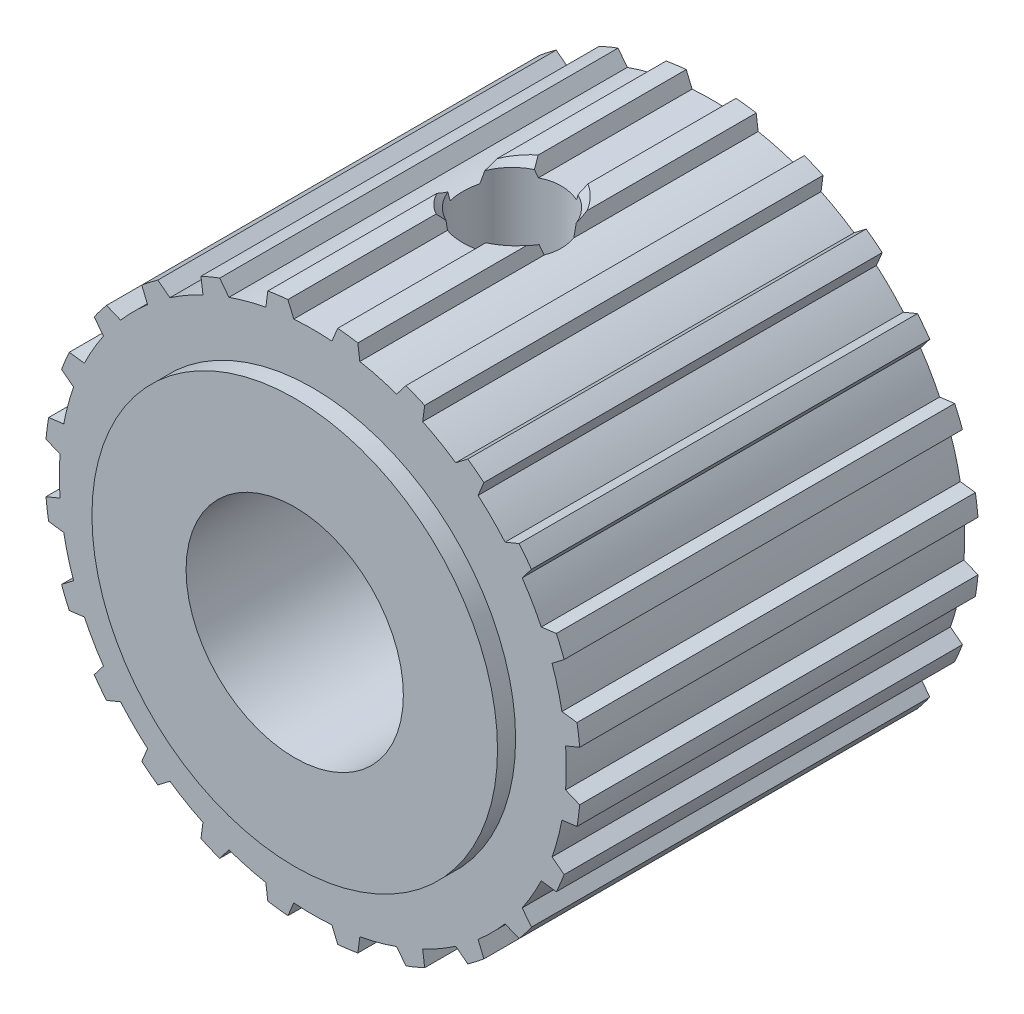
SolidWorks part; units mm, degrees
ref_plane "Face" through (0, 0, 0) normal (0, 0, 1) x (1, 0, 0)
ref_plane "Dessus" through (0, 0, 0) normal (0, 1, 0) x (1, 0, 0)
ref_plane "Droite" through (0, 0, 0) normal (1, 0, 0) x (0, 0, -1)
sketch "Esquisse1" plane through (0, 0, 0) normal (0, 0, 1) x (1, 0, 0)
  line L0 (0, 0) -> (0, 69.2099) construction
  circle A0 centre (0, 0) radius 7.5
  circle A1 centre (0, 0) radius 18.5
  dimension "D1" = 37
  dimension "D2" = 15
extrude "Base-Extrusion" add sketch "Esquisse1" along normal mid plane 30
sketch "Esquisse9" plane through (0, 0, 0) normal (1, 0, 0) x (0, 0, -1)
  line L0 (-15, 18.5) -> (15, 18.5)
  line L1 (-15, 18.5) -> (15, 18.5)
  line L2 (15, -18.5) -> (-15, -18.5)
sketch "Esquisse2" plane through (0, 0, 15) normal (0, 0, 1) x (1, 0, 0)
  line L0 (0, 0) -> (-2.4147, 18.3417) construction
  line L1 (0, 0) -> (2.4147, 18.3417) construction
  line L2 (1.3172, 17.4504) -> (1.7188, 18.42)
  line L3 (-1.3168, 17.4504) -> (-1.7184, 18.42)
  line L4 (0.0002, 17.5) -> (0.0002, 18.5) construction
  arc A0 (1.3172, 17.4504) -> (-1.3168, 17.4504) centre (0, 0) ccw
  circle A1 centre (0, 0) radius 18.5 construction
  arc A3 (1.7188, 18.42) -> (-1.7184, 18.42) centre (0, 0) ccw
  dimension "D2" = 17.5
  dimension "D1" = 15
  dimension "D3" = 15
  dimension "D4" = 15
  dimension "D5" = 2.6339
  dimension "D6" = 0.9722
extrude "Enlèv. mat.-Extru.1" cut sketch "Esquisse2" against normal through all
pattern_circular "Répétition circulaire1" count 24 over 360 about axis through (0, 0, 15) along (0, 0, -1) of "Enlèv. mat.-Extru.1"
ref_plane "Plan4" through (0, 0, 0) normal (0, 0, 1) x (1, 0, 0)
sketch "Esquisse3" plane through (0, 0, -15) normal (0, 0, -1) x (-1, 0, 0)
  circle A0 centre (0, 0) radius 14
  circle A1 centre (0, 0) radius 18.5
  arc A2 (6.4277, -17.3475) -> (7.7218, -16.8114) centre (0, 0) ccw construction
  dimension "D1" = 28
extrude "Enlèv. mat.-Extru.2" cut sketch "Esquisse3" against normal blind 1.25
sketch "Esquisse4" plane through (0, 0, 15) normal (0, 0, 1) x (1, 0, 0)
  circle A0 centre (0, 0) radius 18.5
  circle A1 centre (0, 0) radius 14
  arc A2 (17.3476, 6.4273) -> (16.8116, 7.7215) centre (0, 0) ccw construction
  dimension "D1" = 28
extrude "Enlèv. mat.-Extru.3" cut sketch "Esquisse4" against normal blind 1.25
sketch "Esquisse11" plane through (0, 0, 0) normal (1, 0, 0) x (0, 0, -1)
  line L0 (0, 18.5) -> (0, 0) construction
  line L1 (-15, 18.5) -> (15, 18.5) construction
ref_plane "Plan5" through (0, 18.5, 0) normal (0, -1, 0) x (1, 0, 0)
hole_wizard "Trou taraudé M8x1.251" positions "Esquisse13" profile "Esquisse12" tap size "M8x1.25" standard "ISO" end condition up to next
sketch "Esquisse13" plane through (0, 18.5, 0) normal (0, -1, 0) x (1, 0, 0)
  point P0 (0, 0)
sketch "Esquisse12" plane through (0, 18.5, 0) normal (1, 0, 0) x (0, 0, 1)
  line L0 (0, 0) -> (0, 11)
  line L1 (0, 11) -> (3.4, 11)
  line L2 (3.4, 11) -> (3.4, 0.6)
  line L3 (3.4, 0.6) -> (4, 0)
  line L5 (4, 0) -> (0, 0)
  line L6 (-3.4, 0.6) -> (-4, 0) construction
  line L11 (0, -6.35) -> (0, 107.95) construction
  dimension "Diamètre du trou pour taraudage jusqu'au prochain" = 6.8
  dimension "Profondeur du trou pour taraudage jusqu'au prochain" = 11
  dimension "Diamètre du fraisage entrant" = 8
  dimension "Angle du fraisage entrant" = 90
cosmetic thread "Représentation de filetage1" parameters "D2"=8
